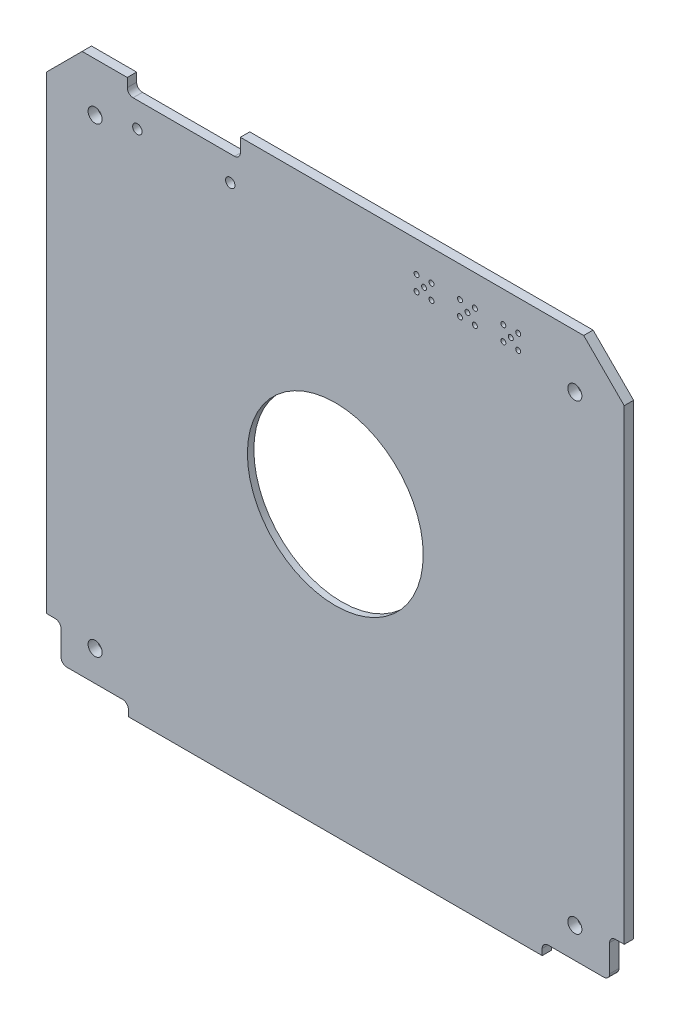
SolidWorks part; units mm, degrees
ref_plane "Front Plane" through (0, 0, 0) normal (0, 0, 1) x (1, 0, 0)
ref_plane "Top Plane" through (0, 0, 0) normal (0, 1, 0) x (1, 0, 0)
ref_plane "Right Plane" through (0, 0, 0) normal (1, 0, 0) x (0, 0, -1)
ref_plane "Plane1" through (0, 0, -0.0125) normal (0, 0, -1) x (-1, 0, 0)
sketch "Sketch1" plane through (0, 0, -0.0125) normal (0, 0, -1) x (-1, 0, 0)
  line L0 (-49.3, 46.115) -> (-49.3, -49.065)
  line L1 (-49.3, -49.065) -> (49.3, -49.065)
  line L2 (49.3, -49.065) -> (49.3, 46.115)
  line L3 (49.3, 46.115) -> (-49.3, 46.115)
extrude "Boss-Extrude1" add sketch "Sketch1" against normal blind 1.6
hole_wizard "Hole1" positions "Sketch3" profile "Sketch2" legacy
sketch "Sketch3" plane through (0, 0, -0.0125) normal (0, 0, -1) x (-1, 0, 0)
  point P0 (-31.21, 40.87)
sketch "Sketch2" plane through (31.21, 40.87, -0.0125) normal (1, 0, 0) x (0, 1, 0)
  line L0 (0, 0) -> (0, 1.6)
  line L1 (0, 1.6) -> (0.425, 1.6)
  line L2 (0.425, 1.6) -> (0.425, 0)
  line L3 (0.425, 0) -> (0, 0)
  line L4 (0, 110) -> (0, -10) construction
  dimension "Diameter" = 0.85
  dimension "Depth" = 1.6
hole_wizard "Hole2" positions "Sketch5" profile "Sketch4" legacy
sketch "Sketch5" plane through (0, 0, -0.0125) normal (0, 0, -1) x (-1, 0, 0)
  point P0 (-28.67, 40.87)
sketch "Sketch4" plane through (28.67, 40.87, -0.0125) normal (1, 0, 0) x (0, 1, 0)
  line L0 (0, 0) -> (0, 1.6)
  line L1 (0, 1.6) -> (0.425, 1.6)
  line L2 (0.425, 1.6) -> (0.425, 0)
  line L3 (0.425, 0) -> (0, 0)
  line L4 (0, 110) -> (0, -10) construction
  dimension "Diameter" = 0.85
  dimension "Depth" = 1.6
hole_wizard "Hole3" positions "Sketch7" profile "Sketch6" legacy
sketch "Sketch7" plane through (0, 0, -0.0125) normal (0, 0, -1) x (-1, 0, 0)
  point P0 (-29.94, 39.6)
sketch "Sketch6" plane through (29.94, 39.6, -0.0125) normal (1, 0, 0) x (0, 1, 0)
  line L0 (0, 0) -> (0, 1.6)
  line L1 (0, 1.6) -> (0.425, 1.6)
  line L2 (0.425, 1.6) -> (0.425, 0)
  line L3 (0.425, 0) -> (0, 0)
  line L4 (0, 110) -> (0, -10) construction
  dimension "Diameter" = 0.85
  dimension "Depth" = 1.6
hole_wizard "Hole4" positions "Sketch9" profile "Sketch8" legacy
sketch "Sketch9" plane through (0, 0, -0.0125) normal (0, 0, -1) x (-1, 0, 0)
  point P0 (-31.21, 38.33)
sketch "Sketch8" plane through (31.21, 38.33, -0.0125) normal (1, 0, 0) x (0, 1, 0)
  line L0 (0, 0) -> (0, 1.6)
  line L1 (0, 1.6) -> (0.425, 1.6)
  line L2 (0.425, 1.6) -> (0.425, 0)
  line L3 (0.425, 0) -> (0, 0)
  line L4 (0, 110) -> (0, -10) construction
  dimension "Diameter" = 0.85
  dimension "Depth" = 1.6
hole_wizard "Hole5" positions "Sketch11" profile "Sketch10" legacy
sketch "Sketch11" plane through (0, 0, -0.0125) normal (0, 0, -1) x (-1, 0, 0)
  point P0 (-28.67, 38.33)
sketch "Sketch10" plane through (28.67, 38.33, -0.0125) normal (1, 0, 0) x (0, 1, 0)
  line L0 (0, 0) -> (0, 1.6)
  line L1 (0, 1.6) -> (0.425, 1.6)
  line L2 (0.425, 1.6) -> (0.425, 0)
  line L3 (0.425, 0) -> (0, 0)
  line L4 (0, 110) -> (0, -10) construction
  dimension "Diameter" = 0.85
  dimension "Depth" = 1.6
hole_wizard "Hole6" positions "Sketch13" profile "Sketch12" legacy
sketch "Sketch13" plane through (0, 0, -0.0125) normal (0, 0, -1) x (-1, 0, 0)
  point P0 (-23.81, 40.87)
sketch "Sketch12" plane through (23.81, 40.87, -0.0125) normal (1, 0, 0) x (0, 1, 0)
  line L0 (0, 0) -> (0, 1.6)
  line L1 (0, 1.6) -> (0.425, 1.6)
  line L2 (0.425, 1.6) -> (0.425, 0)
  line L3 (0.425, 0) -> (0, 0)
  line L4 (0, 110) -> (0, -10) construction
  dimension "Diameter" = 0.85
  dimension "Depth" = 1.6
hole_wizard "Hole7" positions "Sketch15" profile "Sketch14" legacy
sketch "Sketch15" plane through (0, 0, -0.0125) normal (0, 0, -1) x (-1, 0, 0)
  point P0 (-21.27, 40.87)
sketch "Sketch14" plane through (21.27, 40.87, -0.0125) normal (1, 0, 0) x (0, 1, 0)
  line L0 (0, 0) -> (0, 1.6)
  line L1 (0, 1.6) -> (0.425, 1.6)
  line L2 (0.425, 1.6) -> (0.425, 0)
  line L3 (0.425, 0) -> (0, 0)
  line L4 (0, 110) -> (0, -10) construction
  dimension "Diameter" = 0.85
  dimension "Depth" = 1.6
hole_wizard "Hole8" positions "Sketch17" profile "Sketch16" legacy
sketch "Sketch17" plane through (0, 0, -0.0125) normal (0, 0, -1) x (-1, 0, 0)
  point P0 (-22.54, 39.6)
sketch "Sketch16" plane through (22.54, 39.6, -0.0125) normal (1, 0, 0) x (0, 1, 0)
  line L0 (0, 0) -> (0, 1.6)
  line L1 (0, 1.6) -> (0.425, 1.6)
  line L2 (0.425, 1.6) -> (0.425, 0)
  line L3 (0.425, 0) -> (0, 0)
  line L4 (0, 110) -> (0, -10) construction
  dimension "Diameter" = 0.85
  dimension "Depth" = 1.6
hole_wizard "Hole9" positions "Sketch19" profile "Sketch18" legacy
sketch "Sketch19" plane through (0, 0, -0.0125) normal (0, 0, -1) x (-1, 0, 0)
  point P0 (-23.81, 38.33)
sketch "Sketch18" plane through (23.81, 38.33, -0.0125) normal (1, 0, 0) x (0, 1, 0)
  line L0 (0, 0) -> (0, 1.6)
  line L1 (0, 1.6) -> (0.425, 1.6)
  line L2 (0.425, 1.6) -> (0.425, 0)
  line L3 (0.425, 0) -> (0, 0)
  line L4 (0, 110) -> (0, -10) construction
  dimension "Diameter" = 0.85
  dimension "Depth" = 1.6
hole_wizard "Hole10" positions "Sketch21" profile "Sketch20" legacy
sketch "Sketch21" plane through (0, 0, -0.0125) normal (0, 0, -1) x (-1, 0, 0)
  point P0 (-21.27, 38.33)
sketch "Sketch20" plane through (21.27, 38.33, -0.0125) normal (1, 0, 0) x (0, 1, 0)
  line L0 (0, 0) -> (0, 1.6)
  line L1 (0, 1.6) -> (0.425, 1.6)
  line L2 (0.425, 1.6) -> (0.425, 0)
  line L3 (0.425, 0) -> (0, 0)
  line L4 (0, 110) -> (0, -10) construction
  dimension "Diameter" = 0.85
  dimension "Depth" = 1.6
hole_wizard "Hole11" positions "Sketch23" profile "Sketch22" legacy
sketch "Sketch23" plane through (0, 0, -0.0125) normal (0, 0, -1) x (-1, 0, 0)
  point P0 (-16.41, 40.87)
sketch "Sketch22" plane through (16.41, 40.87, -0.0125) normal (1, 0, 0) x (0, 1, 0)
  line L0 (0, 0) -> (0, 1.6)
  line L1 (0, 1.6) -> (0.425, 1.6)
  line L2 (0.425, 1.6) -> (0.425, 0)
  line L3 (0.425, 0) -> (0, 0)
  line L4 (0, 110) -> (0, -10) construction
  dimension "Diameter" = 0.85
  dimension "Depth" = 1.6
hole_wizard "Hole12" positions "Sketch25" profile "Sketch24" legacy
sketch "Sketch25" plane through (0, 0, -0.0125) normal (0, 0, -1) x (-1, 0, 0)
  point P0 (-13.87, 40.87)
sketch "Sketch24" plane through (13.87, 40.87, -0.0125) normal (1, 0, 0) x (0, 1, 0)
  line L0 (0, 0) -> (0, 1.6)
  line L1 (0, 1.6) -> (0.425, 1.6)
  line L2 (0.425, 1.6) -> (0.425, 0)
  line L3 (0.425, 0) -> (0, 0)
  line L4 (0, 110) -> (0, -10) construction
  dimension "Diameter" = 0.85
  dimension "Depth" = 1.6
hole_wizard "Hole13" positions "Sketch27" profile "Sketch26" legacy
sketch "Sketch27" plane through (0, 0, -0.0125) normal (0, 0, -1) x (-1, 0, 0)
  point P0 (-15.14, 39.6)
sketch "Sketch26" plane through (15.14, 39.6, -0.0125) normal (1, 0, 0) x (0, 1, 0)
  line L0 (0, 0) -> (0, 1.6)
  line L1 (0, 1.6) -> (0.425, 1.6)
  line L2 (0.425, 1.6) -> (0.425, 0)
  line L3 (0.425, 0) -> (0, 0)
  line L4 (0, 110) -> (0, -10) construction
  dimension "Diameter" = 0.85
  dimension "Depth" = 1.6
hole_wizard "Hole14" positions "Sketch29" profile "Sketch28" legacy
sketch "Sketch29" plane through (0, 0, -0.0125) normal (0, 0, -1) x (-1, 0, 0)
  point P0 (-16.41, 38.33)
sketch "Sketch28" plane through (16.41, 38.33, -0.0125) normal (1, 0, 0) x (0, 1, 0)
  line L0 (0, 0) -> (0, 1.6)
  line L1 (0, 1.6) -> (0.425, 1.6)
  line L2 (0.425, 1.6) -> (0.425, 0)
  line L3 (0.425, 0) -> (0, 0)
  line L4 (0, 110) -> (0, -10) construction
  dimension "Diameter" = 0.85
  dimension "Depth" = 1.6
hole_wizard "Hole15" positions "Sketch31" profile "Sketch30" legacy
sketch "Sketch31" plane through (0, 0, -0.0125) normal (0, 0, -1) x (-1, 0, 0)
  point P0 (-13.87, 38.33)
sketch "Sketch30" plane through (13.87, 38.33, -0.0125) normal (1, 0, 0) x (0, 1, 0)
  line L0 (0, 0) -> (0, 1.6)
  line L1 (0, 1.6) -> (0.425, 1.6)
  line L2 (0.425, 1.6) -> (0.425, 0)
  line L3 (0.425, 0) -> (0, 0)
  line L4 (0, 110) -> (0, -10) construction
  dimension "Diameter" = 0.85
  dimension "Depth" = 1.6
hole_wizard "Hole16" positions "Sketch33" profile "Sketch32" legacy
sketch "Sketch33" plane through (0, 0, -0.0125) normal (0, 0, -1) x (-1, 0, 0)
  point P0 (17.925, 38.54)
sketch "Sketch32" plane through (-17.925, 38.54, -0.0125) normal (1, 0, 0) x (0, 1, 0)
  line L0 (0, 0) -> (0, 1.6)
  line L1 (0, 1.6) -> (0.8, 1.6)
  line L2 (0.8, 1.6) -> (0.8, 0)
  line L3 (0.8, 0) -> (0, 0)
  line L4 (0, 110) -> (0, -10) construction
  dimension "Diameter" = 1.6
  dimension "Depth" = 1.6
hole_wizard "Hole17" positions "Sketch35" profile "Sketch34" legacy
sketch "Sketch35" plane through (0, 0, -0.0125) normal (0, 0, -1) x (-1, 0, 0)
  point P0 (33.775, 38.54)
sketch "Sketch34" plane through (-33.775, 38.54, -0.0125) normal (1, 0, 0) x (0, 1, 0)
  line L0 (0, 0) -> (0, 1.6)
  line L1 (0, 1.6) -> (0.8, 1.6)
  line L2 (0.8, 1.6) -> (0.8, 0)
  line L3 (0.8, 0) -> (0, 0)
  line L4 (0, 110) -> (0, -10) construction
  dimension "Diameter" = 1.6
  dimension "Depth" = 1.6
hole_wizard "#2 Clearance Hole1" positions "Sketch37" profile "Sketch36" hole size "#2" standard "ANSI Inch"
sketch "Sketch37" plane through (0, 0, -0.0125) normal (0, 0, -1) x (-1, 0, 0)
  point P0 (40.9862, 36.9926)
sketch "Sketch36" plane through (-40.9862, 36.9926, -0.0125) normal (1, 0, 0) x (0, 1, 0)
  line L0 (0, 0) -> (0, 1.6)
  line L1 (0, 1.6) -> (1.2, 1.6)
  line L2 (1.2, 1.6) -> (1.2, 0)
  line L5 (1.2, 0) -> (0, 0)
  line L11 (0, -6.35) -> (0, 107.95) construction
  dimension "Thru Hole Dia." = 2.4
  dimension "Thru Hole Depth" = 1.6
hole_wizard "#2 Clearance Hole2" positions "Sketch39" profile "Sketch38" hole size "#2" standard "ANSI Inch"
sketch "Sketch39" plane through (0, 0, -0.0125) normal (0, 0, -1) x (-1, 0, 0)
  point P0 (-40.8728, 36.9926)
sketch "Sketch38" plane through (40.8728, 36.9926, -0.0125) normal (1, 0, 0) x (0, 1, 0)
  line L0 (0, 0) -> (0, 1.6)
  line L1 (0, 1.6) -> (1.2, 1.6)
  line L2 (1.2, 1.6) -> (1.2, 0)
  line L5 (1.2, 0) -> (0, 0)
  line L11 (0, -6.35) -> (0, 107.95) construction
  dimension "Thru Hole Dia." = 2.4
  dimension "Thru Hole Depth" = 1.6
hole_wizard "#2 Clearance Hole3" positions "Sketch41" profile "Sketch40" hole size "#2" standard "ANSI Inch"
sketch "Sketch41" plane through (0, 0, -0.0125) normal (0, 0, -1) x (-1, 0, 0)
  point P0 (-40.8728, -41.8022)
sketch "Sketch40" plane through (40.8728, -41.8022, -0.0125) normal (1, 0, 0) x (0, 1, 0)
  line L0 (0, 0) -> (0, 1.6)
  line L1 (0, 1.6) -> (1.2, 1.6)
  line L2 (1.2, 1.6) -> (1.2, 0)
  line L5 (1.2, 0) -> (0, 0)
  line L11 (0, -6.35) -> (0, 107.95) construction
  dimension "Thru Hole Dia." = 2.4
  dimension "Thru Hole Depth" = 1.6
hole_wizard "#2 Clearance Hole4" positions "Sketch43" profile "Sketch42" hole size "#2" standard "ANSI Inch"
sketch "Sketch43" plane through (0, 0, -0.0125) normal (0, 0, -1) x (-1, 0, 0)
  point P0 (40.9862, -41.8022)
sketch "Sketch42" plane through (-40.9862, -41.8022, -0.0125) normal (1, 0, 0) x (0, 1, 0)
  line L0 (0, 0) -> (0, 1.6)
  line L1 (0, 1.6) -> (1.2, 1.6)
  line L2 (1.2, 1.6) -> (1.2, 0)
  line L5 (1.2, 0) -> (0, 0)
  line L11 (0, -6.35) -> (0, 107.95) construction
  dimension "Thru Hole Dia." = 2.4
  dimension "Thru Hole Depth" = 1.6
ref_plane "Plane2" through (0, 0, 0.4875) normal (0, 0, 1) x (1, 0, 0)
sketch "Sketch44" plane through (0, 0, 0.4875) normal (0, 0, 1) x (1, 0, 0)
  circle A0 centre (0, 0) radius 38.5
extrude "Cut-Extrude1" cut sketch "Sketch44" against normal up to next
hole_wizard "Hole18" positions "Sketch46" profile "Sketch45" legacy
sketch "Sketch46" plane through (0, 0, 1.5875) normal (0, 0, 1) x (1, 0, 0)
  point P0 (0, 0)
sketch "Sketch45" plane through (0, 0, 1.5875) normal (1, 0, 0) x (0, -1, 0)
  line L0 (0, 0) -> (0, 1.6)
  line L1 (0, 1.6) -> (15, 1.6)
  line L2 (15, 1.6) -> (15, 0)
  line L3 (15, 0) -> (0, 0)
  line L4 (0, 110) -> (0, -10) construction
  dimension "Diameter" = 30
  dimension "Depth" = 1.6
ref_plane "Plane3" through (0, -47, 0) normal (0, 1, 0) x (1, 0, 0)
sketch "Sketch47" plane through (0, -47, 0) normal (0, 1, 0) x (1, 0, 0)
  line L0 (49.3, 0.0125) -> (35.3, 0.0125)
  line L1 (35.3, 0.0125) -> (35.3, -1.5875)
  line L2 (35.3, -1.5875) -> (49.3, -1.5875)
  line L3 (49.3, -1.5875) -> (49.3, 0.0125)
extrude "Cut-Extrude2" cut sketch "Sketch47" against normal up to next
ref_plane "Plane4" through (46.8, 0, 0) normal (-1, 0, 0) x (0, -1, 0)
sketch "Sketch48" plane through (46.8, 0, 0) normal (-1, 0, 0) x (0, -1, 0)
  line L0 (47, 1.5875) -> (40.4, 1.5875)
  line L1 (40.4, 1.5875) -> (40.4, -0.0125)
  line L2 (40.4, -0.0125) -> (47, -0.0125)
  line L3 (47, -0.0125) -> (47, 1.5875)
extrude "Cut-Extrude3" cut sketch "Sketch48" against normal up to next
ref_plane "Plane5" through (-46.8, 0, 0) normal (1, 0, 0) x (0, 0, -1)
sketch "Sketch49" plane through (-46.8, 0, 0) normal (1, 0, 0) x (0, 0, -1)
  line L0 (0.0125, -49.065) -> (0.0125, -40.8)
  line L1 (0.0125, -40.8) -> (-1.5875, -40.8)
  line L2 (-1.5875, -40.8) -> (-1.5875, -49.065)
  line L3 (-1.5875, -49.065) -> (0.0125, -49.065)
extrude "Cut-Extrude4" cut sketch "Sketch49" against normal up to next
sketch "Sketch50" plane through (0, -47, 0) normal (0, 1, 0) x (1, 0, 0)
  line L0 (-35.3, 0.0125) -> (-46.8, 0.0125)
  line L1 (-46.8, 0.0125) -> (-46.8, -1.5875)
  line L2 (-46.8, -1.5875) -> (-35.3, -1.5875)
  line L3 (-35.3, -1.5875) -> (-35.3, 0.0125)
extrude "Cut-Extrude5" cut sketch "Sketch50" against normal up to next
ref_plane "Plane6" through (0, 45.3, 0) normal (0, -1, 0) x (1, 0, 0)
sketch "Sketch51" plane through (0, 45.3, 0) normal (0, -1, 0) x (1, 0, 0)
  line L0 (-16.2, 1.5875) -> (-49.3, 1.5875)
  line L1 (-49.3, 1.5875) -> (-49.3, -0.0125)
  line L2 (-49.3, -0.0125) -> (-16.2, -0.0125)
  line L3 (-16.2, -0.0125) -> (-16.2, 1.5875)
extrude "Cut-Extrude6" cut sketch "Sketch51" against normal up to next
ref_plane "Plane7" through (0, 42.8, 0) normal (0, -1, 0) x (1, 0, 0)
sketch "Sketch52" plane through (0, 42.8, 0) normal (0, -1, 0) x (1, 0, 0)
  line L0 (-35.5, -0.0125) -> (-16.2, -0.0125)
  line L1 (-16.2, -0.0125) -> (-16.2, 1.5875)
  line L2 (-16.2, 1.5875) -> (-35.5, 1.5875)
  line L3 (-35.5, 1.5875) -> (-35.5, -0.0125)
extrude "Cut-Extrude7" cut sketch "Sketch52" against normal up to next
chamfer "Chamfer1" distance 6.915 angle 45 1 edges at (49.3, 46.115, 0.7875)
chamfer "Chamfer2" distance 6.1 angle 45 1 edges at (-49.3, 45.3, 0.7875)
fillet "Fillet1" radius 1 8 edges at (35.3, -47, 0.7875) (-46.8, -40.8, 0.7875) (-35.3, -47, 0.7875) (-16.2, 42.8, 0.7875) (-46.8, -47, 0.7875) (46.8, -47, 0.7875) (46.8, -40.4, 0.7875) (-35.5, 42.8, 0.7875) tangent propagation no
